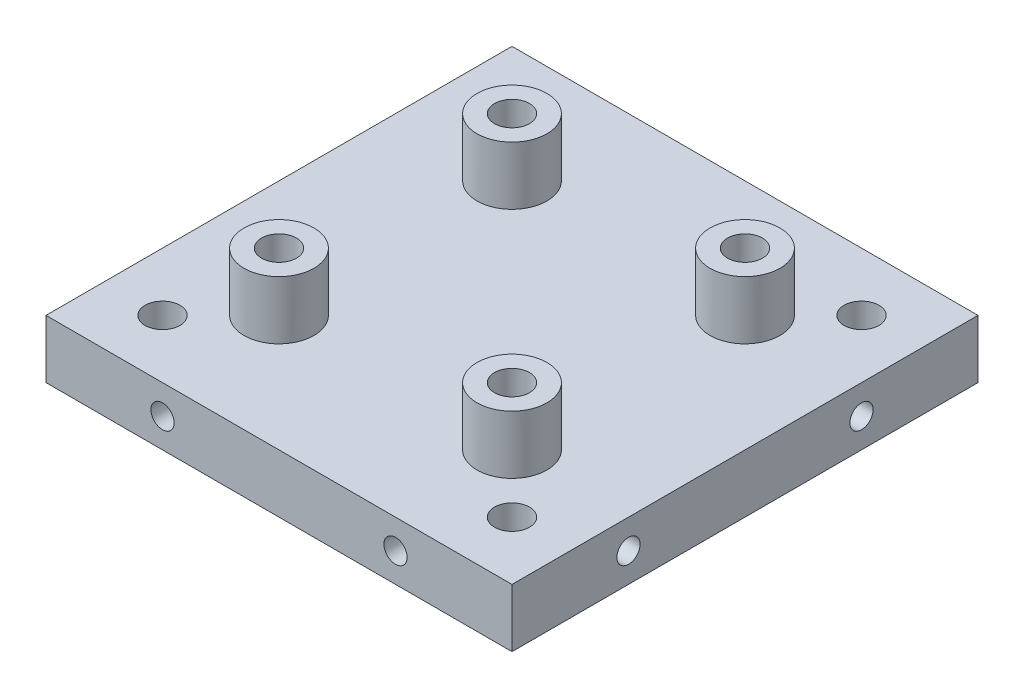
SolidWorks part; units mm, degrees
material "PET"
ref_plane "Front Plane" through (0, 0, 0) normal (0, 0, 1) x (1, 0, 0)
ref_plane "Top Plane" through (0, 0, 0) normal (0, 1, 0) x (1, 0, 0)
ref_plane "Right Plane" through (0, 0, 0) normal (1, 0, 0) x (0, 0, -1)
sketch "Sketch1" plane through (0, 0, 0) normal (0, 1, 0) x (1, 0, 0)
  line L1 (-20, -20) -> (20, -20)
  line L2 (-20, -20) -> (-20, 20)
  line L3 (-20, 20) -> (20, 20)
  line L4 (20, -20) -> (20, 20)
  line L5 (-20, -20) -> (20, 20) construction
  line L6 (-20, 20) -> (20, -20) construction
  point P0 (0, 0)
  dimension "D1" = 40
  dimension "D2" = 40
extrude "Boss-Extrude1" add sketch "Sketch1" along normal blind 5
sketch "Sketch3" plane through (0, 5, 0) normal (0, 1, 0) x (1, 0, 0)
  line L0 (13, 11) -> (18, 11)
  line L5 (-18, -11) -> (18, -11)
  line L6 (-18, -11) -> (-18, 11)
  line L7 (-18, 11) -> (18, 11)
  line L8 (18, -11) -> (18, 11)
  line L9 (-18, -11) -> (18, 11) construction
  line L10 (-18, 11) -> (18, -11) construction
  line L11 (-20, -9) -> (-16, -9)
  line L12 (-20, -9) -> (-20, 9)
  line L13 (-20, 9) -> (-16, 9)
  line L14 (-16, -9) -> (-16, 9)
  line L15 (-20, -9) -> (-16, 9) construction
  line L16 (-20, 9) -> (-16, -9) construction
  line L17 (18, 11) -> (13, 11)
  line L18 (18, 11) -> (18, 6)
  line L19 (18, 6) -> (13, 6)
  line L20 (13, 11) -> (13, 6)
  line L21 (20, 13) -> (20, 4)
  line L22 (20, 4) -> (11, 4)
  line L23 (11, 13) -> (11, 4)
  line L24 (20, 13) -> (11, 13)
  line L25 (-11, 13) -> (-11, 4)
  line L26 (-11, 4) -> (-20, 4)
  line L27 (-20, 13) -> (-20, 4)
  line L28 (-11, 13) -> (-20, 13)
  line L29 (-11, -4) -> (-11, -13)
  line L30 (-11, -13) -> (-20, -13)
  line L31 (-20, -4) -> (-20, -13)
  line L32 (-11, -4) -> (-20, -4)
  line L33 (20, -4) -> (20, -13)
  line L34 (20, -13) -> (11, -13)
  line L35 (11, -4) -> (11, -13)
  line L36 (20, -4) -> (11, -4)
  line L37 (13, 16) -> (13, 13)
  line L38 (-19, 16) -> (-13, 16)
  line L39 (-19, 16) -> (-19, 13)
  line L40 (-19, 13) -> (-13, 13)
  line L41 (-13, 16) -> (-13, 13)
  line L42 (13, 16) -> (19, 16)
  line L43 (19, 16) -> (19, 13)
  line L44 (13, 13) -> (19, 13)
  line L45 (13, -13) -> (13, -16)
  line L46 (13, -13) -> (19, -13)
  line L47 (19, -13) -> (19, -16)
  line L48 (13, -16) -> (19, -16)
  line L49 (-19, -13) -> (-19, -16)
  line L50 (-19, -13) -> (-13, -13)
  line L51 (-13, -13) -> (-13, -16)
  line L52 (-19, -16) -> (-13, -16)
  circle A0 centre (16, 16) radius 1
  circle A1 centre (-16, 16) radius 1
  circle A2 centre (-16, -16) radius 1
  circle A3 centre (16, -16) radius 1
  circle A4 centre (-16, 16) radius 3
  circle A5 centre (16, 16) radius 3
  circle A6 centre (-16, -16) radius 3
  circle A7 centre (16, -16) radius 3
  point P0 (0, 0)
  point P14 (0, 0)
  point P19 (-18, 0)
  line M24 (20, -20) -> (20, 20)
  line M26 (-20, 20) -> (-20, -20)
  dimension "D3" = 22
  dimension "D1" = 32
  dimension "D2" = 32
  dimension "D4" = 36
  dimension "D5" = 18
  dimension "D6" = 5
  dimension "D7" = 5
  dimension "D10" = 6
  dimension "D8" = 2
  dimension "D9" = 2
  dimension "D11" = 2
  dimension "D12" = 2
extrude "Boss-Extrude3" add sketch "Sketch3" along normal blind 5 contours L38 A4 A1 | A4 L38 A1 | L25 L28 L40 L13 L6 L7 M26 | L24 L44 L23 L7 L0 L8 L22 M24 | A5 L37 L44 | A5 L24 L43 | A5 L42 A0 | L42 A5 A0 | L36 L8 L5 L35 L34 L46 M24 | L48 A7 A3 | L52 A6 A2 | L52 A2 | L30 L29 L5 L6 L11 L50 M26 | L41 L40 L39 L38 | L47 L48 L45 L46 | L51 L52 L49 L50 | A3 region at (12, 5, -11.1273) region at (-16.1364, 5, -11.6364) region at (13.6701, 5, -13.6701) region at (19, 5, 4.1273) region at (18.3299, 5, -13.6701) region at (16, 5, -14.6207) region at (16, 5, -17.3793) region at (-16, 5, -14.6207) region at (-16, 5, -17.3793) region at (-16.1364, 5, 11.6364) region at (16, 5, 17.3793) region at (-16, 5, 17.3793) region at (-16, 5, 15.5756)
extrude "Cut-Extrude1" cut sketch "Sketch3<4>" along normal blind 5 contours A3 | A2 | A1
sketch "Sketch3<4>" plane through (0, 5, 0) normal (0, 1, 0) x (1, 0, 0) same geometry as "Sketch3"
sketch "Sketch4" plane through (-20, 0, 0) normal (-1, 0, 0) x (0, 0, 1)
  circle A0 centre (-10, 2.5) radius 1
  circle A1 centre (10, 2.5) radius 1
extrude "Cut-Extrude2" cut sketch "Sketch4" against normal blind 10
pattern_circular "CirPattern2" count 4 every 90 about axis through (0, 0, 0) along (0, -1, 0) of "Cut-Extrude2"
sketch "Sketch6" plane through (0, 0, 0) normal (0, -1, 0) x (1, 0, 0)
  line L1 (-15, -15) -> (15, -15)
  line L2 (-15, -15) -> (-15, 15)
  line L3 (-15, 15) -> (15, 15)
  line L4 (15, -15) -> (15, 15)
  line L5 (-15, -15) -> (15, 15) construction
  line L6 (-15, 15) -> (15, -15) construction
  circle A0 centre (-15, 15) radius 1.5
  circle A1 centre (15, 15) radius 1.5
  circle A2 centre (-15, -15) radius 1.5
  circle A3 centre (15, -15) radius 1.5
  point P0 (0, 0)
  dimension "D1" = 30
  dimension "D2" = 30
extrude "Cut-Extrude5" cut sketch "Sketch6" against normal blind 47 contours A2 | A3 | A1 | A0
sketch "Sketch9" plane through (0, 0, 20) normal (0, 0, 1) x (1, 0, 0)
  line L1 (-20, 5) -> (20, 5)
  line L2 (-20, 5) -> (-20, 10)
  line L3 (-20, 10) -> (20, 10)
  line L4 (20, 5) -> (20, 10)
extrude "Cut-Extrude6" cut sketch "Sketch9" against normal blind 47
sketch "Sketch10" plane through (0, 5, 0) normal (0, 1, 0) x (1, 0, 0)
  line L5 (-10, -10) -> (10, 10) construction
  line L6 (-10, 10) -> (10, -10) construction
  circle A0 centre (-10, 10) radius 3
  circle A1 centre (10, 10) radius 3
  circle A2 centre (-10, -10) radius 3
  circle A3 centre (10, -10) radius 3
  circle A4 centre (-10, 10) radius 1.5
  circle A5 centre (10, 10) radius 1.5
  circle A6 centre (-10, -10) radius 1.5
  circle A7 centre (10, -10) radius 1.5
  point P0 (0, 0)
  dimension "D1" = 20
  dimension "D2" = 20
extrude "Boss-Extrude4" add sketch "Sketch10" along normal blind 5
